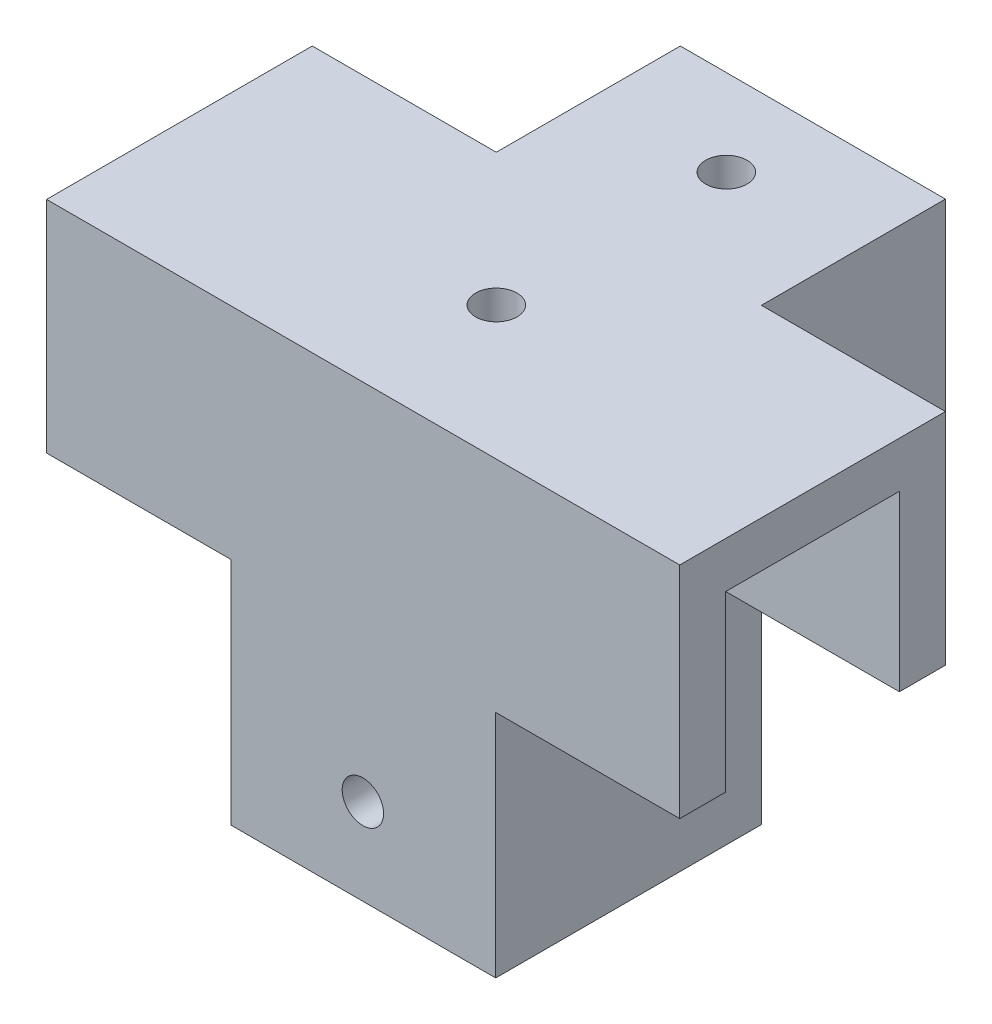
SolidWorks part; units mm, degrees
ref_plane "前视基准面" through (0, 0, 0) normal (0, 0, 1) x (1, 0, 0)
ref_plane "上视基准面" through (0, 0, 0) normal (0, 1, 0) x (1, 0, 0)
ref_plane "右视基准面" through (0, 0, 0) normal (1, 0, 0) x (0, 0, -1)
sketch "草图1" plane through (0, 0, 0) normal (0, 1, 0) x (1, 0, 0)
  line L1 (-22.0308, -9.7154) -> (33.0192, -9.7154)
  line L2 (-22.0308, -9.7154) -> (-22.0308, -13.7154)
  line L3 (-22.0308, -13.7154) -> (33.0192, -13.7154)
  line L4 (33.0192, -9.7154) -> (33.0192, -13.7154)
  line L5 (-22.0308, 9.3846) -> (-6.0308, 9.3846)
  line L6 (-22.0308, 9.3846) -> (-22.0308, 5.3846)
  line L7 (-22.0308, 5.3846) -> (-2.0308, 5.3846)
  line L8 (-2.0308, 9.3846) -> (-2.0308, 5.3846)
  line L9 (-2.0308, 5.3846) -> (-6.0308, 5.3846)
  line L10 (-2.0308, 5.3846) -> (-2.0308, 25.3846)
  line L11 (-2.0308, 25.3846) -> (-6.0308, 25.3846)
  line L12 (-6.0308, 9.3846) -> (-6.0308, 25.3846)
  line L13 (33.0192, 5.3846) -> (13.0192, 5.3846)
  line L14 (33.0192, 5.3846) -> (33.0192, 9.3846)
  line L15 (33.0192, 9.3846) -> (17.0192, 9.3846)
  line L16 (13.0192, 5.3846) -> (13.0192, 8.7692)
  line L17 (13.0192, 5.3846) -> (22.6654, 5.3846)
  line L18 (13.0192, 5.3846) -> (13.0192, 25.3846)
  line L19 (13.0192, 25.3846) -> (17.0192, 25.3846)
  line L20 (17.0192, 9.3846) -> (17.0192, 25.3846)
  dimension "D1" = 4
  dimension "D2" = 4
  dimension "D3" = 4
  dimension "D4" = 4
  dimension "D5" = 4
  dimension "D6" = 15.1
  dimension "D7" = 15.05
  dimension "D8" = 20
  dimension "D9" = 16
  dimension "D10" = 16
  dimension "D11" = 20
  dimension "D12" = 0
  dimension "D13" = 0
extrude "凸台-拉伸1" add sketch "草图1" along normal blind 15.1 contours L12 L5 L6 L7 L8 L10 L11 | L15 L20 L19 L18 L16 L13 L14 | L4 L1 L2 L3 region at (5.4942, 0, 11.7154) region at (-14.0308, 0, -9.1018) region at (27.8423, 0, -5.6675)
sketch "草图2" plane through (0, 15.1, 0) normal (0, 1, 0) x (1, 0, 0)
  line L1 (-22.0308, 9.3846) -> (33.0192, 9.3846)
  line L2 (-22.0308, 9.3846) -> (-22.0308, -13.7154)
  line L3 (-22.0308, -13.7154) -> (33.0192, -13.7154)
  line L4 (33.0192, 9.3846) -> (33.0192, -13.7154)
  line L5 (-6.0308, 25.3846) -> (17.0192, 25.3846)
  line L6 (-6.0308, 25.3846) -> (-6.0308, 9.3846)
  line L7 (-6.0308, 9.3846) -> (17.0192, 9.3846)
  line L8 (17.0192, 25.3846) -> (17.0192, 9.3846)
  line M1 (-6.0308, 25.3846) -> (-6.0308, 9.3846)
  line M2 (-6.0308, 9.3846) -> (-22.0308, 9.3846)
  line M3 (-22.0308, 9.3846) -> (-22.0308, 5.3846)
  line M4 (-22.0308, 5.3846) -> (-2.0308, 5.3846)
  line M5 (-2.0308, 5.3846) -> (-2.0308, 25.3846)
  line M6 (-2.0308, 25.3846) -> (-6.0308, 25.3846)
extrude "凸台-拉伸2" add sketch "草图2" along normal blind 4 contours L1 M1 M5 M6 | L8 L5 L1 M5 | L4 L1 L2 L3 M5 M4 | L1 M2 M3 M4 M5 region at (-12.0308, 15.1, -7.3846) region at (-4.0308, 15.1, -17.3846) region at (6.6707, 15.1, 2.8065) region at (7.4942, 15.1, -17.3846)
sketch "草图3" plane through (0, 0, 0) normal (0, -1, 0) x (1, 0, 0)
  line L0 (-22.0308, 13.7154) -> (33.0192, 13.7154) construction
  line L1 (17.0192, -9.3846) -> (-5.9808, -9.3846)
  line L2 (17.0192, -9.3846) -> (17.0192, 13.7154)
  line L3 (17.0192, 13.7154) -> (-5.9808, 13.7154)
  line L4 (-5.9808, -9.3846) -> (-5.9808, 13.7154)
  line L5 (-22.0308, 9.7154) -> (33.0192, 9.7154) construction
  line L6 (13.0192, -5.3846) -> (-2.1308, -5.3846)
  line L7 (13.0192, -5.3846) -> (13.0192, 9.7154)
  line L8 (13.0192, 9.7154) -> (-2.1308, 9.7154)
  line L9 (-2.1308, -5.3846) -> (-2.1308, 9.7154)
  dimension "D1" = 23
  dimension "D2" = 15.15
extrude "凸台-拉伸3" add sketch "草图3" along normal blind 20
sketch "草图4" plane through (0, 19.1, 0) normal (0, 1, 0) x (1, 0, 0)
  line L0 (17.0192, 25.3846) -> (-6.0308, 25.3846) construction
  circle A0 centre (5.4692, 17.8846) radius 1.8
  circle A1 centre (5.4692, -2.1154) radius 1.8
  dimension "D1" = 3.6
  dimension "D2" = 3.6
  dimension "D3" = 7.5
extrude "切除-拉伸1" cut sketch "草图4" against normal blind 20
sketch "草图5" plane through (0, 0, 13.7154) normal (0, 0, 1) x (1, 0, 0)
  line L0 (17.0192, -20) -> (-5.9808, -20) construction
  circle A0 centre (5.4692, -12.5) radius 1.8
  dimension "D1" = 3.6
  dimension "D2" = 7.5
extrude "切除-拉伸2" cut sketch "草图5" against normal blind 27
